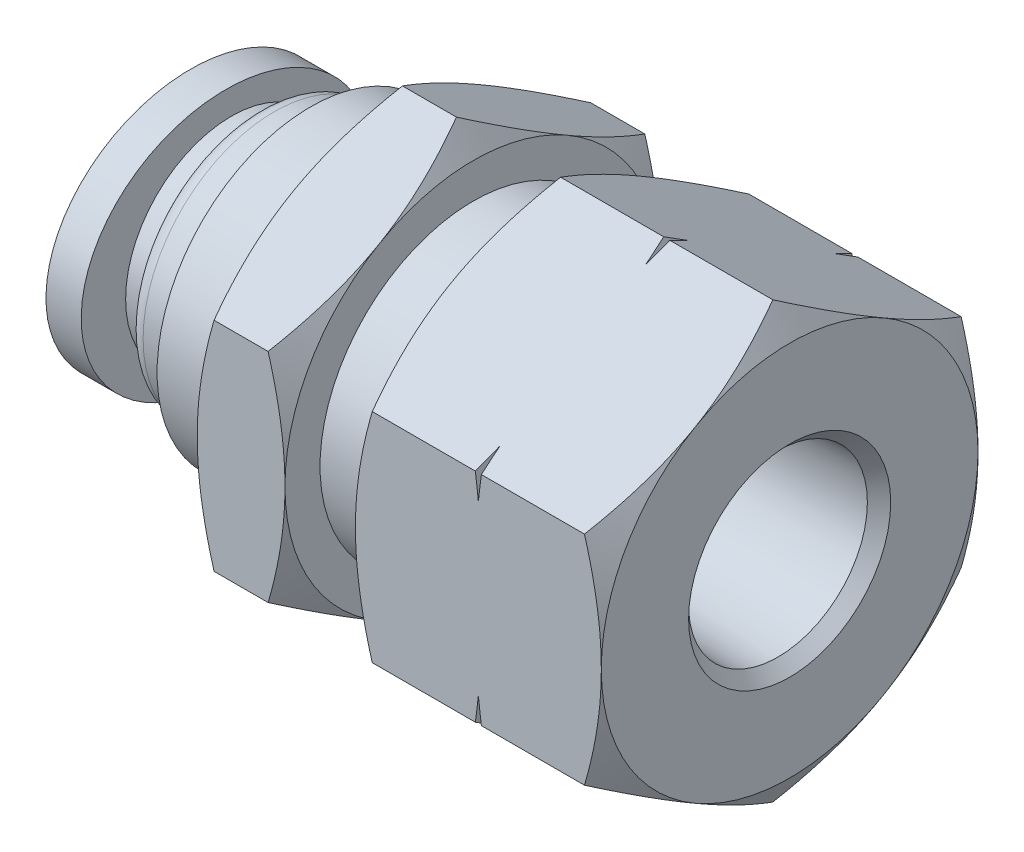
SolidWorks part; units mm, degrees
material "6061-T6 (SS)"
ref_plane "Front Plane" through (0, 0, 0) normal (0, 0, 1) x (1, 0, 0)
ref_plane "Top Plane" through (0, 0, 0) normal (0, 1, 0) x (1, 0, 0)
ref_plane "Right Plane" through (0, 0, 0) normal (1, 0, 0) x (0, 0, -1)
sketch "Sketch1" plane through (0, 0, 0) normal (1, 0, 0) x (0, 0, -1)
  line L1 (0, 9.796) -> (-8.4836, 4.898)
  line L2 (-8.4836, 4.898) -> (-8.4836, -4.898)
  line L3 (-8.4836, -4.898) -> (0, -9.796)
  line L4 (0, -9.796) -> (8.4836, -4.898)
  line L5 (8.4836, -4.898) -> (8.4836, 4.898)
  line L6 (8.4836, 4.898) -> (0, 9.796)
  circle A0 centre (0, 0) radius 8.4836 construction
  dimension "D1" = 16.9672
extrude "Boss-Extrude1" add sketch "Sketch1" along normal mid plane 26.9875
sketch "Sketch2" plane through (0, 0, 0) normal (0, 0, 1) x (1, 0, 0)
  line L0 (13.4937, 0) -> (-13.4937, 0) construction
  line L1 (13.4937, 4.898) -> (13.4937, -4.898) construction
  line L2 (-13.4937, 4.898) -> (-13.4937, -4.898) construction
  line L3 (13.4937, 9.796) -> (13.4937, 8.4836)
  line L4 (13.4937, 9.796) -> (13.4937, 4.898) construction
  line L5 (13.4937, 8.4836) -> (12.736, 9.796)
  line L6 (13.4937, 9.796) -> (-13.4937, 9.796) construction
  line L7 (12.736, 9.796) -> (13.4937, 9.796)
  line L8 (3.1771, 9.796) -> (-1.5134, 9.796)
  line L9 (-1.5134, 9.796) -> (-0.7557, 8.4836)
  line L10 (-0.7557, 8.4836) -> (-0.7557, 6.9024)
  line L11 (-0.7557, 6.9024) -> (2.4193, 6.9024)
  line L12 (2.4193, 6.9024) -> (2.4193, 8.4836)
  line L13 (2.4193, 8.4836) -> (3.1771, 9.796)
  line L14 (7.8204, 9.796) -> (7.9566, 9.288)
  line L15 (7.9566, 9.288) -> (8.0927, 9.796)
  line L16 (8.0927, 9.796) -> (7.8204, 9.796)
  line L17 (-3.9476, 9.796) -> (-4.7053, 8.4836)
  line L18 (-4.7053, 8.4836) -> (-4.7053, 6.9024)
  line L19 (-4.7053, 6.9024) -> (-8.0962, 6.9024)
  line L20 (-8.0962, 6.9024) -> (-8.0962, 5.9055)
  line L21 (-8.0962, 5.9055) -> (-9.7218, 5.9055)
  line L22 (-10.4838, 5.1435) -> (-10.4838, 4.7625)
  line L23 (-10.4838, 4.7625) -> (-11.6522, 4.7625)
  line L24 (-11.6522, 4.7625) -> (-11.6522, 3.81)
  line L25 (-11.6522, 3.81) -> (-13.4937, 3.81)
  line L26 (2.8838, 9.288) -> (13.0293, 9.288) construction
  line L27 (13.4937, 4.0437) -> (4.1973, 3.7401)
  line L28 (4.1973, 3.7401) -> (3.4971, 2.5273)
  line L29 (3.4971, 2.5273) -> (2.2542, 2.5273)
  line L30 (2.2542, 2.5273) -> (2.2542, 3.81)
  line L31 (-13.4937, 0) -> (-13.4937, 3.3147)
  line L32 (-13.4937, 3.3147) -> (-5.8737, 3.3147)
  line L33 (-5.8737, 3.3147) -> (-5.8737, 3.81)
  line L34 (-5.8737, 3.81) -> (2.2542, 3.81)
  line L35 (13.4937, 4.0437) -> (13.4937, 0)
  line L36 (13.4937, 0) -> (-13.4937, 0)
  line L37 (-13.4937, 3.81) -> (-13.4937, 9.796)
  line L38 (-13.4937, 9.796) -> (-3.9476, 9.796)
  arc A0 (-9.7218, 5.9055) -> (-10.4838, 5.1435) centre (-9.7218, 5.1435) ccw
  dimension "D13" = 0.762
  dimension "D1" = 30
  dimension "D2" = 0.508
  dimension "D3" = 60
  dimension "D4" = 11.0744
  dimension "D5" = 16.9672
  dimension "D6" = 13.8049
  dimension "D7" = 3.175
  dimension "D8" = 3.9497
  dimension "D9" = 11.811
  dimension "D10" = 23.9776
  dimension "D11" = 21.59
  dimension "D12" = 9.525
  dimension "D14" = 7.62
  dimension "D15" = 25.146
  dimension "D16" = 1.87
  dimension "D17" = 7.4803
  dimension "D18" = 9.2964
  dimension "D19" = 60
  dimension "D20" = 5.0546
  dimension "D21" = 6.6294
  dimension "D22" = 15.748
  dimension "D23" = 7.62
revolve "Cut-Revolve1" cut sketch "Sketch2" angle 360 about L36
chamfer "Chamfer1" distance 0.508 angle 45 1 edges at (13.4937, 0, -4.0437) first distance on face at (13.4937, 0, -4.0437)
sketch "Sketch3" plane through (-13.4937, 0, 0) normal (-1, 0, 0) x (0, 0, 1)
  circle A0 centre (0, 0) radius 3.3147 construction
  circle A1 centre (0, 0) radius 3.3147
  ellipse E0 centre (0, 0) end of major axis (-6.5088, 0) minor radius 5.6769
  dimension "D1" = 13.0175
  dimension "D2" = 11.3538
extrude "Boss-Extrude2" add sketch "Sketch3" against normal blind 1.5875
